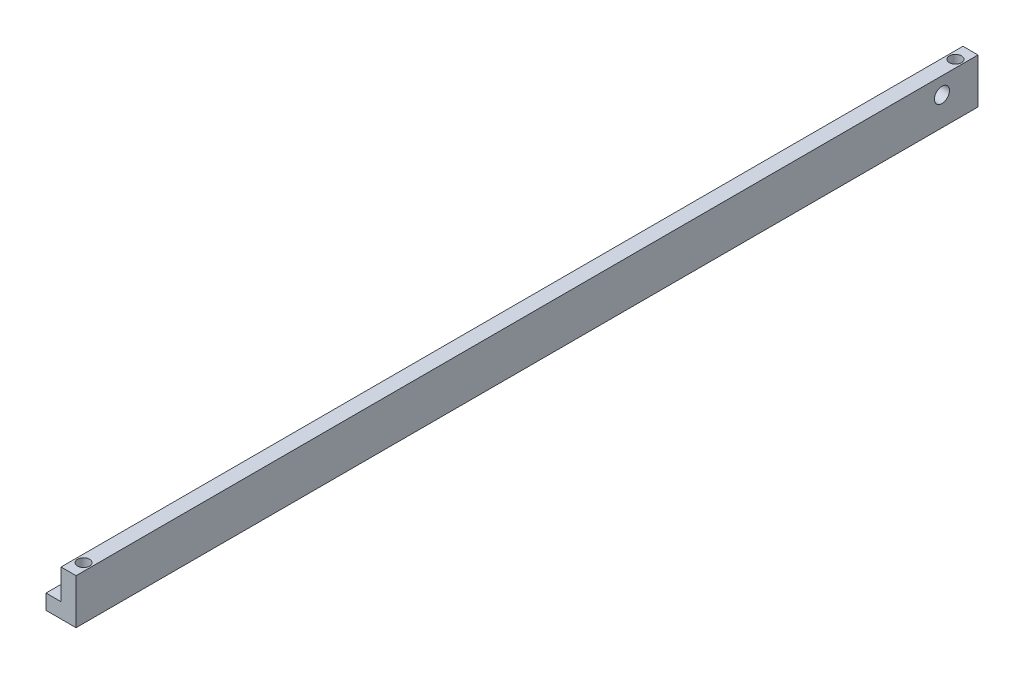
SolidWorks part; units mm, degrees
other "Markup1"
sketch "Sketch6" plane through (0, 0, 0) normal (0.1266, -0.8901, -0.4379) x (-0.2811, -0.4555, 0.8447)
ref_plane "Front Plane" through (0, 0, 0) normal (0, 0, 1) x (1, 0, 0)
ref_plane "Top Plane" through (0, 0, 0) normal (0, 1, 0) x (1, 0, 0)
ref_plane "Right Plane" through (0, 0, 0) normal (1, 0, 0) x (0, 0, -1)
sketch "Sketch1" plane through (0, 0, 0) normal (0, 0, 1) x (1, 0, 0)
  line L0 (0, 0) -> (-6.35, 0)
  line L3 (-6.35, 0) -> (-6.35, 19.05)
  line L4 (-6.35, 19.05) -> (0, 19.05)
  line L5 (0, 19.05) -> (0, 0)
  dimension "D1" = 19.05
  dimension "D4" = 6.35
extrude "Boss-Extrude1" add sketch "Sketch1" along normal blind 381 contours L3 L0 L5 L4 region at (-3.175, 9.525, 0)
sketch "Sketch2" plane through (0, 19.05, 0) normal (0, 1, 0) x (1, 0, 0)
  line L0 (-3.175, 0) -> (-3.175, -381) construction
  line L3 (-6.35, 0) -> (0, 0) construction
  line L4 (-6.35, -381) -> (0, -381) construction
  circle A0 centre (-3.175, -374.65) radius 2.54
  circle A1 centre (-3.175, -6.35) radius 2.54
  dimension "D1" = 5.08
  dimension "D2" = 6.35
  dimension "D3" = 6.35
sketch "Sketch3" plane through (0, 0, 0) normal (0, -1, 0) x (1, 0, 0)
  line L0 (-3.175, 0) -> (-3.175, 381) construction
  line L3 (0, 381) -> (0, 0) construction
  line L4 (0, 0) -> (-6.35, 0) construction
  line L5 (0, 381) -> (-6.35, 381) construction
  circle A0 centre (-3.175, 374.65) radius 2.54
  circle A1 centre (-3.175, 6.35) radius 2.54
  dimension "D2" = 5.08
  dimension "D1" = 3.175
  dimension "D3" = 6.35
  dimension "D4" = 6.35
sketch "Sketch4" plane through (0, 0, 0) normal (1, 0, 0) x (0, 0, -1)
  line L1 (-381, 19.05) -> (-381, 0) construction
  line L3 (-381, 19.05) -> (0, 19.05) construction
  circle A0 centre (-15.24, 12.065) radius 3.175
  dimension "D3" = 6.35
  dimension "D1" = 365.76
  dimension "D2" = 6.985
extrude "Boss-Extrude2" add sketch "Sketch1<3>" along normal blind 25.4 contours L0 region at (-3.175, 9.525, 0)
sketch "Sketch1<3>" plane through (0, 0, 0) normal (0, 0, 1) x (1, 0, 0) same geometry as "Sketch1"
extrude "Cut-Extrude3" cut sketch "Sketch4" against normal blind 25.4
sketch "Sketch5" plane through (0, 0, 381) normal (0, 0, 1) x (1, 0, 0)
  line L1 (-6.35, 0) -> (-12.7, 0)
  line L2 (-6.35, 0) -> (-6.35, 6.35)
  line L3 (-6.35, 6.35) -> (-12.7, 6.35)
  line L4 (-12.7, 0) -> (-12.7, 6.35)
  dimension "D1" = 6.35
  dimension "D2" = 6.35
extrude "Boss-Extrude3" add sketch "Sketch5" against normal blind 35.56
extrude "Cut-Extrude4" cut sketch "Sketch2" against normal blind 7.62
extrude "Cut-Extrude5" cut sketch "Sketch3" against normal blind 7.62
